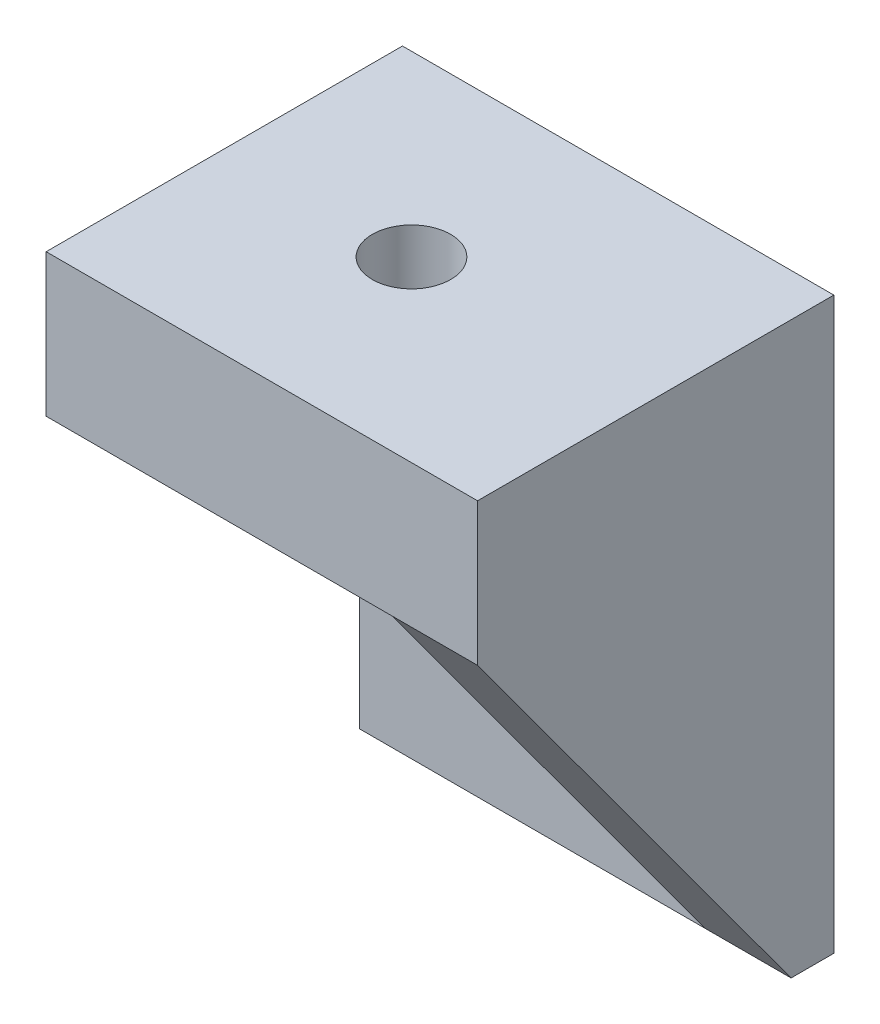
SolidWorks part; units mm, degrees
ref_plane "Front" through (0, 0, 0) normal (0, 0, 1) x (1, 0, 0)
ref_plane "Top" through (0, 0, 0) normal (0, 1, 0) x (1, 0, 0)
ref_plane "Right" through (0, 0, 0) normal (1, 0, 0) x (0, 0, -1)
sketch "Sketch1" plane through (0, 0, 0) normal (0, 1, 0) x (1, 0, 0)
  line L1 (0, 0) -> (15.135, 0)
  line L2 (0, 0) -> (0, 12.5)
  line L3 (0, 12.5) -> (15.135, 12.5)
  line L4 (15.135, 0) -> (15.135, 12.5)
  dimension "D1" = 15.135
  dimension "D2" = 12.5
extrude "base" add sketch "Sketch1" along normal blind 5
sketch "Sketch2" plane through (0, 0, -12.5) normal (0, 0, -1) x (-1, 0, 0)
  line L0 (0, 5) -> (0, 0) construction
  line L1 (-15.135, 0) -> (0, 0)
  line L2 (-15.135, 0) -> (-15.135, -15)
  line L3 (-15.135, -15) -> (0, -15)
  line L4 (0, 0) -> (0, -15)
  dimension "D1" = 15
extrude "Boss-Extrude2" add sketch "Sketch2" against normal blind 1.5
sketch "Sketch3" plane through (0, 0, 0) normal (-1, 0, 0) x (0, 0, 1)
  line L0 (0, 0) -> (-11, -15)
  line L1 (-11, -15) -> (-11, 0)
  line L2 (-11, 0) -> (0, 0)
extrude "Boss-Extrude3" add sketch "Sketch3" against normal up to surface (15.135 mm away) up to face at (15.135, -3.3333, -7.8333)
sketch "Sketch4" plane through (0, 0, 0) normal (0, 0, 1) x (1, 0, 0)
  line L0 (15.135, -15) -> (0, -15) construction
  line L1 (3, 0) -> (12.135, 0)
  line L2 (3, 0) -> (3, -15)
  line L3 (3, -15) -> (12.135, -15)
  line L4 (12.135, 0) -> (12.135, -15)
  line L5 (0, 0) -> (15.135, 0) construction
  line L6 (15.135, 0) -> (15.135, -15) construction
  point P6 (7.5675, 0)
  point P9 (7.5675, 0)
  dimension "D1" = 3
extrude "Cut-Extrude1" cut sketch "Sketch4" against normal up to vertex (11 mm away) up to point (15.135, -15, -11)
sketch "Sketch5" plane through (0, 0, -11) normal (0, 0, 1) x (1, 0, 0)
  line L0 (12.135, 0) -> (3, 0) construction
  line L1 (3, -15) -> (12.135, -15) construction
  circle A0 centre (7.5675, -4) radius 2.3 construction
  circle A1 centre (7.5675, -11) radius 2.3 construction
  circle A2 centre (7.5675, -4) radius 1.375
  circle A3 centre (7.5675, -11) radius 1.375
  point P8 (7.5675, 0)
  dimension "D1" = 4.6
  dimension "D4" = 2.75
  dimension "D2" = 4
  dimension "D3" = 4
extrude "Cut-Extrude2" cut sketch "Sketch5" against normal blind 2
sketch "Sketch6" plane through (0, 5, 0) normal (0, 1, 0) x (1, 0, 0)
  line L1 (0, 0) -> (15.135, 0) construction
  circle A0 centre (6.5675, 6.25) radius 1.375
  dimension "D1" = 2.75
  dimension "D2" = 6.5675
  dimension "D3" = 6.25
extrude "Cut-Extrude3" cut sketch "Sketch6" against normal blind 5.75
sketch "Sketch7" plane through (12.135, 0, 0) normal (-1, 0, 0) x (0, 0, 1)
  line L3 (-11, -15) -> (0, 0)
  line L4 (0, 0) -> (-11, 0)
  line L5 (-11, 0) -> (-11, -15)
  line L6 (-11, -15) -> (0, 0)
  line L7 (0, 0) -> (-11, 0)
  line L8 (-11, 0) -> (-11, -15)
  dimension "D1" = 0
extrude "Cut-Extrude4" cut sketch "Sketch7" along normal blind 25.4852
